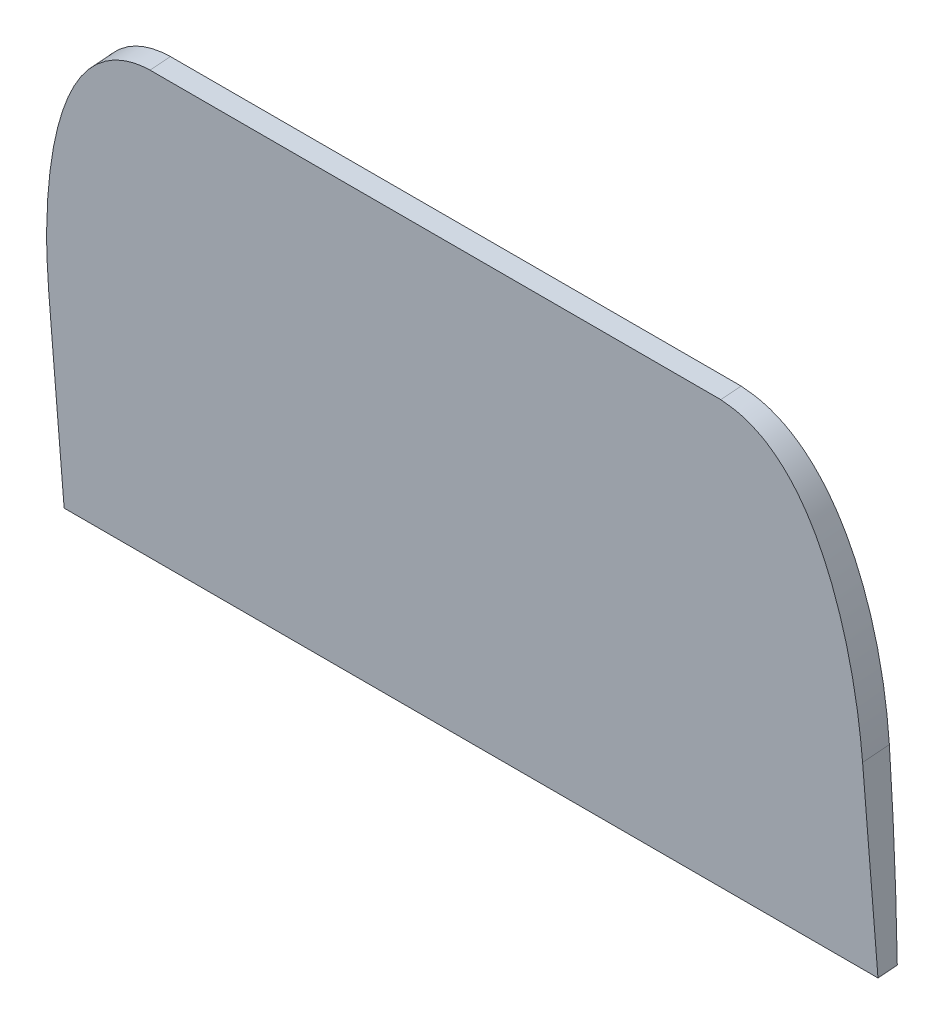
SolidWorks part; units mm, degrees
ref_plane "Front Plane" through (0, 0, 0) normal (0, 0, 1) x (1, 0, 0)
ref_plane "Top Plane" through (0, 0, 0) normal (0, 1, 0) x (1, 0, 0)
ref_plane "Right Plane" through (0, 0, 0) normal (1, 0, 0) x (0, 0, -1)
sketch "Sketch1" plane through (0, 1.9457, -24.5977) normal (0, 0.0789, -0.9969) x (-1, 0, 0)
  line L0 (20.1187, 38.9275) -> (-20.2059, 38.9275)
  line L1 (-28.75, 20.2023) -> (-28.75, 6.4275)
  line L2 (-28.75, 6.4275) -> (28.75, 6.4275)
  line L3 (28.75, 6.4275) -> (28.75, 20.2022)
  line L4 (20.1267, 39.1775) -> (-20.2196, 39.1775)
  line L5 (-29, 20.2039) -> (-29, 6.1775)
  line L6 (-29, 6.1775) -> (29, 6.1775)
  line L7 (29, 6.1775) -> (29, 20.2039)
  line L8 (20.1267, 39.1775) -> (-20.2196, 39.1775) construction
  line L9 (-29, 20.2039) -> (-29, 6.1775)
  line L10 (-29, 6.1775) -> (29, 6.1775)
  line L11 (29, 6.1775) -> (29, 20.2039)
  spline S0 degree 1 poles (28.75, 20.2022) (20.1187, 38.9275) knots 0 0 1 1 construction
  spline S1 degree 1 poles (-20.2059, 38.9275) (-28.75, 20.2023) knots 0 0 1 1 construction
  spline S2 degree 2 poles (33.4866, -3979.6941) (30.0891, -21.5511) (28.9752, 21.6311) (28.9558, 22.3839) (28.9161, 23.0565) (28.8748, 23.7559) (28.8083, 24.4794) (28.7415, 25.206) (28.6558, 25.8992) (28.4749, 27.3631) (28.2027, 28.7148) (27.9021, 30.2074) (27.5124, 31.4821) (27.0665, 32.9404) (26.5032, 34.134) (26.3118, 34.5397) (26.1167, 34.8974) (25.9078, 35.2802) (25.6787, 35.638) (25.3594, 36.1367) (25.0135, 36.5637) (24.5413, 37.1466) (24.0261, 37.596) (23.748, 37.8387) (23.4635, 38.0404) (23.1749, 38.245) (22.8602, 38.4209) (22.4388, 38.6565) (21.9906, 38.8219) (21.7643, 38.9054) (21.537, 38.9685) (21.2069, 39.06) (20.8404, 39.113) (20.6703, 39.1376) (20.4852, 39.1529) (4.9066, 40.4402) (-3974.3495, 245.8887) knots -5.608816 -5.608816 -5.608816 0.0625 0.0625 0.125 0.125 0.1875 0.1875 0.25 0.25 0.375 0.375 0.5 0.5 0.625 0.625 0.6625 0.6625 0.7 0.7 0.75 0.75 0.8125 0.8125 0.84375 0.84375 0.875 0.875 0.916667 0.916667 0.9375 0.9375 0.96875 0.96875 0.984375 0.984375 3.441051 3.441051 3.441051 only from (29, 20.2039) to (20.1267, 39.1775)
  spline S3 degree 2 poles (3955.7962, 474.4382) (-16.0223, 39.662) (-20.5753, 39.1381) (-20.7579, 39.1171) (-20.9286, 39.0899) (-21.3002, 39.0305) (-21.6205, 38.94) (-21.9641, 38.843) (-22.2891, 38.7054) (-22.6103, 38.5695) (-22.9324, 38.3835) (-23.2417, 38.2049) (-23.5307, 37.9927) (-23.8077, 37.7895) (-24.0818, 37.5451) (-24.6042, 37.0792) (-25.0615, 36.5044) (-25.4881, 35.968) (-25.8726, 35.325) (-26.2171, 34.7489) (-26.54, 34.0556) (-27.0956, 32.8627) (-27.5367, 31.4021) (-27.9174, 30.1416) (-28.2121, 28.6679) (-28.48, 27.3286) (-28.6586, 25.8762) (-28.7437, 25.1849) (-28.8098, 24.4628) (-28.8758, 23.7425) (-28.9167, 23.0453) (-28.956, 22.3771) (-28.9753, 21.6255) (-30.0821, -21.4237) (-34.0795, -3979.7119) knots -1.846603 -1.846603 -1.846603 0.015625 0.015625 0.03125 0.03125 0.0625 0.0625 0.09375 0.09375 0.125 0.125 0.15625 0.15625 0.1875 0.1875 0.25 0.25 0.3125 0.3125 0.375 0.375 0.5 0.5 0.625 0.625 0.75 0.75 0.8125 0.8125 0.875 0.875 0.9375 0.9375 6.617157 6.617157 6.617157 only from (-20.2196, 39.1775) to (-29, 20.2039)
  spline S4 degree 2 poles (29, 20.2039) (28.9874, 21.1552) (28.9752, 21.6311) (28.9558, 22.3839) (28.9161, 23.0565) (28.8748, 23.7559) (28.8083, 24.4794) (28.7415, 25.206) (28.6558, 25.8992) (28.4749, 27.3631) (28.2027, 28.7148) (27.9021, 30.2074) (27.5124, 31.4821) (27.0665, 32.9404) (26.5032, 34.134) (26.3118, 34.5397) (26.1167, 34.8974) (25.9078, 35.2802) (25.6787, 35.638) (25.3594, 36.1367) (25.0135, 36.5637) (24.5413, 37.1466) (24.0261, 37.596) (23.748, 37.8387) (23.4635, 38.0404) (23.1749, 38.245) (22.8602, 38.4209) (22.4388, 38.6565) (21.9906, 38.8219) (21.7643, 38.9054) (21.537, 38.9685) (21.2069, 39.06) (20.8404, 39.113) (20.6703, 39.1376) (20.4852, 39.1529) (20.3861, 39.1611) (20.1267, 39.1775) knots 0 0 0 0.0625 0.0625 0.125 0.125 0.1875 0.1875 0.25 0.25 0.375 0.375 0.5 0.5 0.625 0.625 0.6625 0.6625 0.7 0.7 0.75 0.75 0.8125 0.8125 0.84375 0.84375 0.875 0.875 0.916667 0.916667 0.9375 0.9375 0.96875 0.96875 0.984375 0.984375 1 1 1
  spline S5 degree 2 poles (-20.2196, 39.1775) (-20.5371, 39.1425) (-20.5753, 39.1381) (-20.7579, 39.1171) (-20.9286, 39.0899) (-21.3002, 39.0305) (-21.6205, 38.94) (-21.9641, 38.843) (-22.2891, 38.7054) (-22.6103, 38.5695) (-22.9324, 38.3835) (-23.2417, 38.2049) (-23.5307, 37.9927) (-23.8077, 37.7895) (-24.0818, 37.5451) (-24.6042, 37.0792) (-25.0615, 36.5044) (-25.4881, 35.968) (-25.8726, 35.325) (-26.2171, 34.7489) (-26.54, 34.0556) (-27.0956, 32.8627) (-27.5367, 31.4021) (-27.9174, 30.1416) (-28.2121, 28.6679) (-28.48, 27.3286) (-28.6586, 25.8762) (-28.7437, 25.1849) (-28.8098, 24.4628) (-28.8758, 23.7425) (-28.9167, 23.0453) (-28.956, 22.3771) (-28.9753, 21.6255) (-28.9875, 21.1518) (-29, 20.2039) knots 0 0 0 0.015625 0.015625 0.03125 0.03125 0.0625 0.0625 0.09375 0.09375 0.125 0.125 0.15625 0.15625 0.1875 0.1875 0.25 0.25 0.3125 0.3125 0.375 0.375 0.5 0.5 0.625 0.625 0.75 0.75 0.8125 0.8125 0.875 0.875 0.9375 0.9375 1 1 1
  spline S6 degree 2 poles (28.75, 20.2022) (28.7421, 20.7969) (28.7322, 21.3249) (28.7282, 21.5037) (28.7256, 21.6145) (28.7201, 21.8137) (28.713, 22.0402) (28.6978, 22.4461) (28.6598, 23.2085) (28.5645, 24.4597) (28.4144, 25.8637) (28.2364, 27.1233) (28.0883, 27.9901) (27.9617, 28.6544) (27.8042, 29.397) (27.6393, 30.0934) (27.4617, 30.769) (27.2804, 31.3949) (27.0472, 32.1188) (26.8065, 32.7862) (26.5487, 33.4279) (26.3209, 33.939) (26.1204, 34.3525) (25.9244, 34.7328) (25.6227, 35.2654) (25.2344, 35.8633) (24.8307, 36.4029) (24.353, 36.9481) (23.7515, 37.5252) (22.7599, 38.2354) (21.1662, 38.9007) (20.1187, 38.9275) knots 0.000054 0.000054 0.000054 0.039105 0.050821 0.058631 0.066441 0.074251 0.085966 0.109397 0.156258 0.21874 0.281222 0.328083 0.359324 0.390564 0.421805 0.453046 0.484287 0.515528 0.546768 0.578009 0.60925 0.632681 0.648301 0.671732 0.702973 0.734213 0.765454 0.796695 0.843556 0.906038 0.99976 0.99976 0.99976
  spline S7 degree 2 poles (-20.2059, 38.9275) (-20.6341, 38.8925) (-21.2458, 38.7785) (-21.7934, 38.642) (-22.8347, 38.1984) (-23.8034, 37.4789) (-24.4126, 36.8846) (-24.8775, 36.3446) (-25.2748, 35.8053) (-25.6695, 35.1876) (-25.9911, 34.6118) (-26.3246, 33.9351) (-26.5818, 33.3494) (-26.8363, 32.7077) (-27.0741, 32.0397) (-27.305, 31.3133) (-27.4816, 30.6962) (-27.6554, 30.0283) (-27.8168, 29.3403) (-27.9711, 28.6077) (-28.0957, 27.9488) (-28.2416, 27.0896) (-28.4171, 25.8411) (-28.566, 24.4428) (-28.6605, 23.196) (-28.6981, 22.4381) (-28.7132, 22.0336) (-28.7203, 21.8076) (-28.7257, 21.6087) (-28.7283, 21.4985) (-28.7322, 21.3205) (-28.7422, 20.7947) (-28.75, 20.2023) knots 0.000339 0.000339 0.000339 0.039386 0.055005 0.094052 0.156528 0.203384 0.234622 0.265859 0.297097 0.328335 0.359573 0.39081 0.422048 0.453286 0.484523 0.515761 0.546999 0.578236 0.609474 0.640712 0.67195 0.718806 0.781282 0.843757 0.890614 0.914042 0.925756 0.933565 0.941375 0.949184 0.960898 0.999945 0.999945 0.999945
  dimension "D1" = 0
  dimension "D2" = 0.25
extrude "Boss-Extrude1" add sketch "Sketch1" along normal blind 10 contours L0 S7 L1 L2 L3 S6
sketch "Sketch2" plane through (0, 0, 0) normal (1, 0, 0) x (0, 0, -1)
  line L0 (22.1078, 46.0731) -> (43.259, 46.0731)
  line L1 (43.259, 46.0731) -> (43.259, 3.2)
  line L2 (43.259, 3.2) -> (25.5, 3.2)
  spline S0 degree 3 poles (-369.4509, 2954.6148) (-298.1462, -568.0764) (34.1282, -245.883) (24.679, 17.5818) (24.4852, 21.1618) (23.9533, 28.3013) (23.6154, 31.861) (22.976, 37.182) (22.7404, 38.9538) (1.9707, 179.3434) (-172.8584, 258.8686) (-2890.1309, -611.9488) knots -17.851688 -17.851688 -17.851688 -17.851688 0.25 0.25 0.5 0.5 0.75 0.75 0.875 0.875 10.691544 10.691544 10.691544 10.691544 only from (25, 3.2) to (21.6158, 45.984) construction
  spline S1 degree 3 poles (25, 3.2) (25, 6.8026) (24.9364, 10.4036) (24.679, 17.5818) (24.4852, 21.1618) (23.9533, 28.3013) (23.6154, 31.861) (22.976, 37.182) (22.7404, 38.9538) (22.2181, 42.4842) (21.9319, 44.2398) (21.6158, 45.984) knots 0 0 0 0 0.25 0.25 0.5 0.5 0.75 0.75 0.875 0.875 1 1 1 1
  spline S2 degree 1 poles (25.5, 3.2) (22.1078, 46.0731) knots 0 0 1 1 construction
  spline S3 degree 3 poles (25.5, 3.2) (25.5, 6.8041) (25.3725, 14.0233) (24.7904, 24.776) (23.7729, 35.4849) (22.7452, 42.5565) (22.1078, 46.0731) knots 0 0 0 0 0.25 0.5 0.75 1 1 1 1
  dimension "D1" = 0.5
extrude "Cut-Extrude1" cut sketch "Sketch2" against normal through all and the other way through all contours S3 L2 L1 L0 region at (0, 25.2625, -33.8163)
